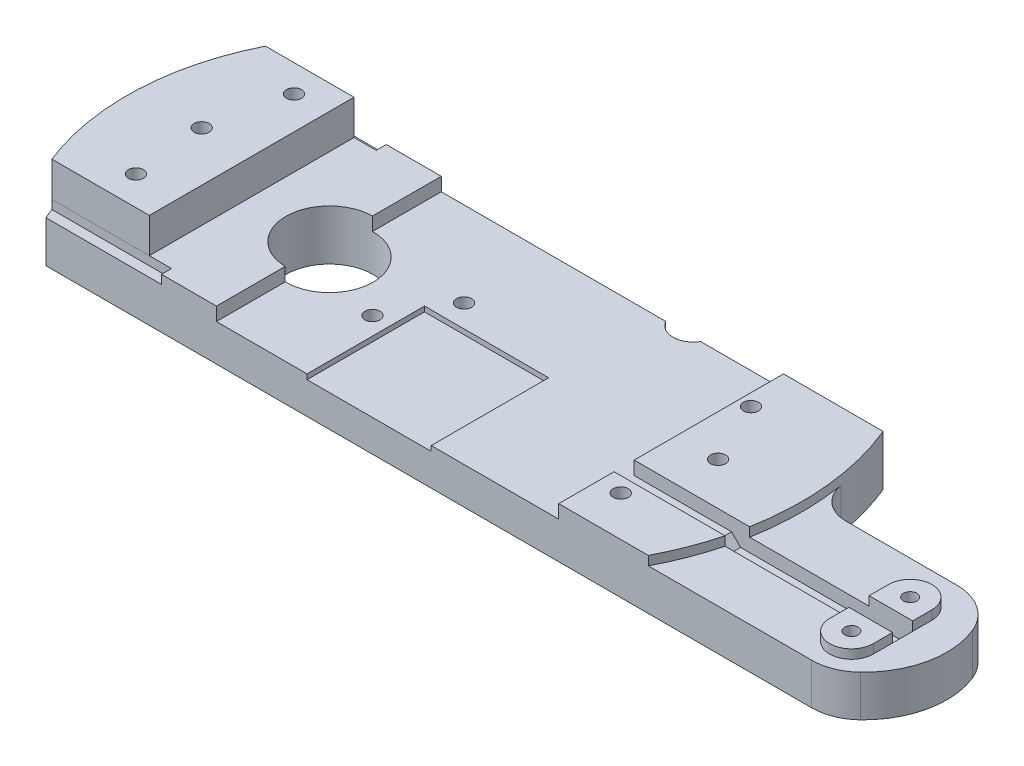
SolidWorks part; units mm, degrees
material "1060 Alloy"
ref_plane "Front Plane" through (0, 0, 0) normal (0, 0, 1) x (1, 0, 0)
ref_plane "Top Plane" through (0, 0, 0) normal (0, 1, 0) x (1, 0, 0)
ref_plane "Right Plane" through (0, 0, 0) normal (1, 0, 0) x (0, 0, -1)
sketch "Sketch1" plane through (0, 0, 0) normal (0, 1, 0) x (1, 0, 0)
  line L1 (-97.5, -33.5) -> (97.5, -33.5)
  line L2 (-97.5, -33.5) -> (-97.5, 33.5)
  line L3 (-97.5, 33.5) -> (97.5, 33.5)
  line L4 (97.5, -33.5) -> (97.5, 33.5)
  line L5 (-97.5, -33.5) -> (97.5, 33.5) construction
  line L6 (-97.5, 33.5) -> (97.5, -33.5) construction
  point P0 (0, 0)
  dimension "D1" = 67
  dimension "D2" = 195
extrude "Boss-Extrude1" add sketch "Sketch1" along normal blind 25.4
sketch "Sketch2" plane through (0, 0, 0) normal (0, -1, 0) x (1, 0, 0)
  line L0 (-97.5, -33.5) -> (-97.5, 33.5) construction
  line L1 (97.5, 33.5) -> (97.5, -33.5) construction
  line L2 (97.5, 33.5) -> (88.5, 33.5)
  line L3 (-97.5, 33.5) -> (97.5, 33.5) construction
  line L4 (97.5, -33.5) -> (91.5, -33.5)
  line L5 (97.5, -33.5) -> (-97.5, -33.5) construction
  line L6 (-97.5, 33.5) -> (-91, 33.5)
  line L7 (-97.5, -33.5) -> (-88, -33.5)
  circle A0 centre (18.0922, -3.2198) radius 79.4078
  circle A1 centre (-22.6589, 2.9929) radius 74.8411
  line M7 (97.5, -33.5) -> (97.5, 33.5)
  line M8 (97.5, 33.5) -> (-97.5, 33.5)
  line M9 (-97.5, 33.5) -> (-97.5, -33.5)
  line M10 (-97.5, -33.5) -> (97.5, -33.5)
  dimension "D1" = 9
  dimension "D2" = 6
  dimension "D3" = 6.5
  dimension "D4" = 9.5
extrude "Cut-Extrude1" cut sketch "Sketch2" against normal through all contours A0 M7 M8 | A0 M10 M7 | A1 M9 M10 | A1 M8 M9 region at (94.8284, 0, 24.4273) region at (95.7123, 0, -25.9883) region at (-95.5654, 0, 25.941) region at (-94.6839, 0, -24.4966)
sketch "Sketch3" plane through (0, 0, 33.5) normal (0, 0, -1) x (-1, 0, 0)
  line L0 (97.5, 25.4) -> (63.2, 25.4)
  line L2 (63.2, 25.4) -> (63.2, 15)
  line L3 (63.2, 15) -> (40.2, 15)
  line L4 (40.2, 15) -> (40.2, 11)
  line L5 (40.2, 11) -> (-61.8, 11)
  line L6 (-91.5, 25.4) -> (88, 25.4) construction
  line L10 (97.5, 0) -> (97.5, 25.4) construction
  line L11 (-61.8, 11) -> (-61.8, 15)
  line L12 (-61.8, 15) -> (-97.5, 15)
  line L13 (-97.5, 25.4) -> (-97.5, 0) construction
  line L14 (-97.5, 15) -> (-97.5, 25.4)
  line L15 (-97.5, 25.4) -> (63.2, 25.4)
  line M13 (-88.5, 0) -> (-88.5, 25.4)
  line M14 (-88.5, 25.4) -> (91, 25.4)
  dimension "D1" = 10.4
  dimension "D2" = 34.3
  dimension "D3" = 23
  dimension "D4" = 4
  dimension "D5" = 102
extrude "Cut-Extrude2" cut sketch "Sketch3" along normal through all contours L11 L12 L2 L3 L4 L5 M13 M14 | L2 L3 L4 L5 L11 L12 L14 L15 region at (12.2699, 18.7206, 33.5)
sketch "Sketch4" plane through (0, 25.4, 0) normal (0, 1, 0) x (1, 0, 0)
  line L0 (-56.5873, 33.5) -> (-56.5873, 30.5)
  line L1 (-63.2, 33.5) -> (-88, 33.5) construction
  line L2 (-56.5873, 30.5) -> (-89.5873, 30.5)
  line L3 (-56.5873, -33.5) -> (-56.5873, -30.5)
  line L4 (-91, -33.5) -> (-63.2, -33.5) construction
  line L5 (-56.5873, -30.5) -> (-92.2617, -30.5)
  line L6 (-56.5873, 33.5) -> (-63.2, 33.5)
  line L7 (-56.5873, -33.5) -> (-63.2, -33.5)
  arc A0 (-88, 33.5) -> (-91, -33.5) centre (-22.6589, -2.9929) ccw construction
  line M5 (-91, -33.5) -> (-63.2, -33.5)
  line M6 (-63.2, -33.5) -> (-63.2, 33.5)
  line M7 (-63.2, 33.5) -> (-88, 33.5)
  arc M8 (-88, 33.5) -> (-91, -33.5) centre (-22.6589, -2.9929) ccw
  dimension "D1" = 3
  dimension "D2" = 3
  dimension "D3" = 33
extrude "Cut-Extrude3" cut sketch "Sketch4" against normal blind 13 contours L2 M6 M7 M8 | L0 L6 L2 M6 | L5 M6 M8 M5 | L7 L3 L5 M6 region at (-59.8937, 25.4, -32) region at (-76.0082, 25.4, -31.9845) region at (-77.4242, 25.4, 31.9889) region at (-59.8937, 25.4, 32)
sketch "Sketch6" plane through (0, 0, 0) normal (0, -1, 0) x (1, 0, 0)
  line L0 (-63.2, -33.5) -> (-97.5, -33.5)
  line L1 (91.5, -33.5) -> (-88, -33.5) construction
  line L2 (-63.2, -33.5) -> (-63.2, 33.5)
  line L3 (-91, 33.5) -> (88.5, 33.5) construction
  line L4 (-63.2, -9) -> (-28.1, -9) construction
  line L5 (-63.2, 8.7) -> (-18.5, 8.7) construction
  line L6 (-63.2, -8.2) -> (-8.1, -8.2) construction
  line L8 (91.5, -33.5) -> (-88, -33.5) construction
  line L9 (-97.5, -33.5) -> (-97.5, 33.5)
  line L10 (-97.5, 33.5) -> (-63.2, 33.5)
  circle A1 centre (-18.5, 8.7) radius 2.25
  circle A2 centre (74.1, -1.7) radius 2.25
  circle A3 centre (68.3, 21.5) radius 2.25
  circle A4 centre (65.4, -20.2) radius 2.25
  circle A5 centre (-8.1, -8.2) radius 2.25
  circle A6 centre (-75.9, 21.8) radius 2.25
  circle A7 centre (-78, 0.1) radius 2.25
  circle A8 centre (-73, -22.4) radius 2.25
  arc A10 (-91, 33.5) -> (-88, -33.5) centre (-22.6589, 2.9929) ccw construction
  dimension "D22" = 4.5
  dimension "D3" = 35.1
  dimension "D4" = 34.3
  dimension "D5" = 44.7
  dimension "D6" = 24.5
  dimension "D7" = 55.1
  dimension "D8" = 42.2
  dimension "D9" = 137.3
  dimension "D10" = 128.6
  dimension "D11" = 131.5
  dimension "D12" = 9.8
  dimension "D13" = 14.8
  dimension "D14" = 12.7
  dimension "D15" = 11.1
  dimension "D16" = 33.6
  dimension "D17" = 55.3
  dimension "D18" = 31.8
  dimension "D19" = 55
  dimension "D20" = 13.3
  dimension "D21" = 25.3
extrude "Cut-Extrude4" cut sketch "Sketch6" against normal through all contours A5 | A1 | A6 | A7 | A8 | A4 | A2 | A3 region at (-18.5, 0, 8.7) region at (74.1, 0, -1.7) region at (68.3, 0, 21.5) region at (65.4, 0, -20.2) region at (-8.1, 0, -8.2) region at (-75.9, 0, 21.8) region at (-78, 0, 0.1) region at (-73, 0, -22.4)
sketch "Sketch7" plane through (0, 11, 0) normal (0, 1, 0) x (1, 0, 0)
  line L1 (-13.2, 1.5) -> (23.8, 1.5)
  line L2 (-13.2, 1.5) -> (-13.2, -33.5)
  line L3 (-13.2, -33.5) -> (23.8, -33.5)
  line L4 (23.8, 1.5) -> (23.8, -33.5)
  line L8 (-63.2, 30.5) -> (-63.2, -30.5) construction
  line L9 (-63.2, 30.5) -> (-63.2, -30.5) construction
  line L10 (-40.2, -33.5) -> (61.8, -33.5) construction
  dimension "D1" = 50
  dimension "D2" = 87
  dimension "D3" = 35
extrude "Cut-Extrude5" cut sketch "Sketch7" against normal blind 1.5
sketch "Sketch8" plane through (0, 25.4, 0) normal (0, 1, 0) x (1, 0, 0)
  line L0 (-56.5873, -33.5) -> (-97.5, -33.5)
  line L1 (-97.5, -33.5) -> (-97.5, 33.5)
  line L3 (-97.5, 33.5) -> (31.9, 33.5)
  line L6 (31.9, 36.5) -> (31.9, 30.5)
  line L7 (31.9, 33.5) -> (37.0962, 33.5)
  line L10 (-56.5873, 33.5) -> (-88, 33.5) construction
  line L11 (-40.2, 33.5) -> (61.8, 33.5) construction
  circle A1 centre (31.9, 36.5) radius 6
  arc A2 (-89.5873, 30.5) -> (-92.2617, -30.5) centre (-22.6589, -2.9929) ccw construction
  dimension "D1" = 12
  dimension "D2" = 129.4
extrude "Cut-Extrude6" cut sketch "Sketch8" against normal blind 18.5 contours L6 A1 L7 | L3 A1 L6 region at (29.8648, 25.4, -32.2699) region at (33.9352, 25.4, -32.2699)
sketch "Sketch9" plane through (0, 0, 0) normal (0, -1, 0) x (1, 0, 0)
  line L0 (88.5, 33.5) -> (137.2004, 33.5)
  line L1 (139.5727, -7.5) -> (97.3846, -7.5)
  arc A0 (153.4738, 1.8643) -> (147.5429, 29.3643) centre (130.3054, 11.2571) ccw
  arc A1 (91.5, -33.5) -> (88.5, 33.5) centre (18.0922, -3.2198) ccw construction
  arc A2 (142.3827, -10.6321) -> (147.5429, 29.3643) centre (130.3054, 11.2571) ccw construction
  arc A3 (147.5429, 29.3643) -> (137.2004, 33.5) centre (137.2004, 18.5) ccw
  arc A4 (147.5429, 29.3643) -> (137.9704, 33.4802) centre (137.2004, 18.5) ccw construction
  arc A5 (139.5727, -7.5) -> (153.4738, 1.8643) centre (139.5727, 7.5) ccw
  circle A6 centre (112.8181, -27.5) radius 16 construction
  circle A7 centre (103.4238, 59.4942) radius 16 construction
  circle A8 centre (112.8181, -27.5) radius 20 construction
  arc A9 (97.3846, -7.5) -> (88.5, 33.5) centre (18.0922, -3.2198) ccw
  circle A10 centre (138.3, 5.25) radius 2
  circle A11 centre (138.3, 22.75) radius 2
  circle A12 centre (138.3, 22.75) radius 2 construction
  circle A13 centre (138.3, 5.25) radius 2 construction
  point P21 (0, 0)
  point P35 (112.8181, -27.5)
  dimension "D1" = 4
extrude "Boss-Extrude2" add sketch "Sketch9" against normal offset from surface (12.3 mm away) 1.3 up to face at (-16.25, 11, 8.7) offset beyond the face yes
fillet "Fillet1" radius 10 1 edges at (97.3846, 6.15, -7.5)
sketch "Sketch10" plane through (0, 0, 0) normal (0, -1, 0) x (1, 0, 0)
  circle A0 centre (-40.0178, 0) radius 13
  point P2 (-40.0178, 0)
  dimension "D1" = 26
extrude "Cut-Extrude7" cut sketch "Sketch10" against normal through all
sketch "Sketch11" plane through (0, 12.3, 0) normal (0, 1, 0) x (1, 0, 0)
  line L0 (138.3, -5.25) -> (138.3, -22.75) construction
  line L1 (144.8, -5.25) -> (144.8, -22.75)
  line L2 (131.8, -5.25) -> (131.8, -22.75)
  line L3 (131.8, -11) -> (144.8, -11)
  line L4 (131.8, -17) -> (144.8, -17)
  line L5 (131.8, -14) -> (144.8, -14) construction
  arc A0 (144.8, -5.25) -> (131.8, -5.25) centre (138.3, -5.25) ccw
  arc A1 (131.8, -22.75) -> (144.8, -22.75) centre (138.3, -22.75) ccw
  point P4 (138.3, -14)
  circle M15 centre (138.3, -22.75) radius 2
  circle M16 centre (138.3, -5.25) radius 2
  dimension "D1" = 13
  dimension "D2" = 6
extrude "Boss-Extrude3" add sketch "Sketch11" along normal up to surface (2.7 mm away) contours L1 A0 L2 L3 M16 | L2 A1 L1 L4 M15 region at (144.6214, 12.3, 8.125) region at (144.6214, 12.3, 19.875) up to face at (70.55, 15, 21.5)
sketch "Sketch12" plane through (0, 0, 11) normal (0, 0, 1) x (1, 0, 0)
  line L0 (144.8, 15) -> (144.8, 8.3)
  line L1 (144.8, 8.3) -> (93.5, 8.3)
  line L3 (97.5, 12.3) -> (88.5, 12.3) construction
  line L4 (90.8, 11) -> (61.8, 11)
  line L5 (61.8, 11) -> (61.8, 15)
  line L6 (61.8, 15) -> (88.5, 15) construction
  line L7 (61.8, 15) -> (144.8, 15)
  line L10 (97.5, 12.3) -> (93.5, 12.3) construction
  line L12 (88.5, 12.3) -> (137.2004, 12.3) construction
  line L13 (93.5, 12.3) -> (93.5, 8.3) construction
  line L14 (61.8, 11) -> (61.8, 15) construction
  line L15 (23.8, 11) -> (61.8, 11) construction
  line L16 (93.5, 8.3) -> (90.8, 11)
  dimension "D1" = 45
extrude "Cut-Extrude8" cut sketch "Sketch12" along normal up to surface (6 mm away) up to face at (138.3, 13.65, 17)
split "Split1" bodies to split 116 resulting bodies 114 115 split by face at (-52.6367, 15, 0)
